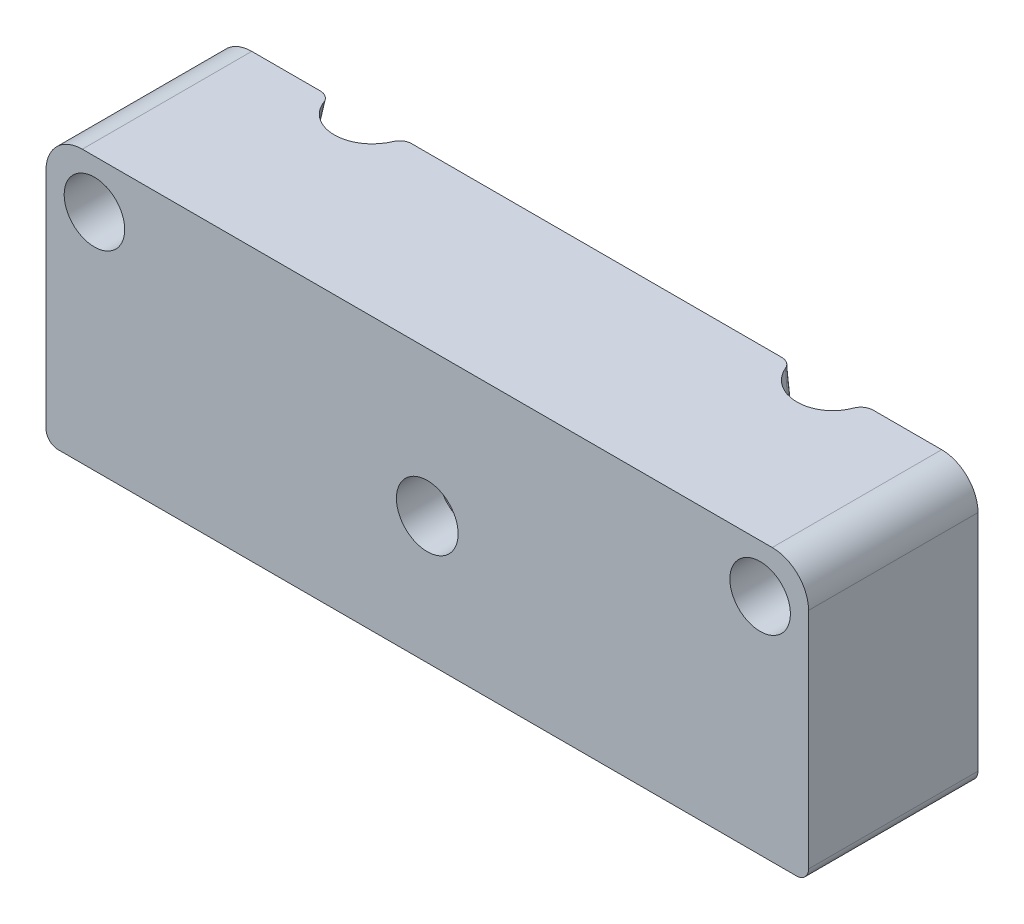
SolidWorks part; units mm, degrees
other "Extruder Parking Post Base" parameters "D3"=9.4899, "D4"=7.1672, "D1"=20.5784, "D2"=74.5967, "D5"=5, "D6"=5, "D7"=3.2, "D8"=4
ref_plane "Front" through (0, 0, 0) normal (0, 0, 1) x (1, 0, 0)
ref_plane "Top" through (0, 0, 0) normal (0, 1, 0) x (1, 0, 0)
ref_plane "Right" through (0, 0, 0) normal (1, 0, 0) x (0, 0, -1)
sketch "Sketch1" plane through (0, 0, 0) normal (0, 1, 0) x (1, 0, 0)
  line L0 (0, 10) -> (8, 10) construction
  line L1 (0, 0) -> (63, 0)
  line L2 (0, 0) -> (0, 20)
  line L3 (0, 20) -> (63, 20)
  line L4 (63, 0) -> (63, 20)
  line L5 (63, 10) -> (55, 10) construction
  circle A0 centre (55, 10) radius 2.65
  circle A1 centre (8, 10) radius 2.65
  dimension "D4" = 5.3
  dimension "D1" = 20
  dimension "D2" = 63
  dimension "D3" = 8
extrude "Boss-Extrude1" add sketch "Sketch1" along normal blind 5
sketch "Sketch2" plane through (0, 5, 0) normal (0, 1, 0) x (1, 0, 0)
  line L0 (31.5, 20) -> (31.5, 0) construction
  line L1 (63, 20) -> (0, 20) construction
  line L2 (0, 0) -> (63, 0) construction
  line L3 (27.5, 8.2) -> (35.5, 8.2)
  line L4 (35.5, 8.2) -> (35.5, 12)
  line L5 (35.5, 12) -> (46.5, 12)
  line L6 (46.5, 12) -> (46.5, 4)
  line L7 (46.5, 4) -> (16.5, 4)
  line L8 (16.5, 12) -> (16.5, 4)
  line L9 (27.5, 12) -> (16.5, 12)
  line L10 (27.5, 8.2) -> (27.5, 12)
  point P15 (31.5, 4)
  point P17 (31.5, 8.2)
  dimension "D1" = 8
  dimension "D2" = 3.8
  dimension "D3" = 30
  dimension "D4" = 4
  dimension "D5" = 8
extrude "Boss-Extrude2" add sketch "Sketch2" along normal blind 22
sketch "Sketch3" plane through (0, 0, -8.2) normal (0, 0, -1) x (-1, 0, 0)
  line L0 (-31.5, 27) -> (-31.5, 19.75) construction
  line L1 (-35.5, 27) -> (-27.5, 27) construction
  line L2 (-31.5, 19.75) -> (-31.5, 16.25) construction
  line L3 (-31.5, 16.25) -> (-31.5, 5) construction
  line L4 (-63, 5) -> (0, 5) construction
  line L5 (-31.5, 19.75) -> (-31.5, 16.25) construction
  line L6 (-29.9, 19.75) -> (-29.9, 16.25)
  line L7 (-33.1, 19.75) -> (-33.1, 16.25)
  arc A0 (-29.9, 19.75) -> (-33.1, 19.75) centre (-31.5, 19.75) ccw
  arc A1 (-33.1, 16.25) -> (-29.9, 16.25) centre (-31.5, 16.25) ccw
  point P9 (-31.5, 18)
  dimension "D2" = 1.6
  dimension "D1" = 13
  dimension "D3" = 3.5
extrude "Cut-Extrude1" cut sketch "Sketch3" against normal through all
fillet "Fillet1" radius 2 4 edges at (0, 2.5, -20) (0, 2.5, 0) (63, 2.5, -20) (63, 2.5, 0)
ref_plane "Plane1" through (0, 8, 0) normal (0, 1, 0) x (1, 0, 0)
sketch "Sketch4" plane through (0, 0, -4) normal (0, 0, 1) x (1, 0, 0)
  line L0 (31.5, 0) -> (31.5, 30) construction
  line L1 (2, 0) -> (61, 0) construction
  line L2 (0, 30) -> (63, 30)
  line L3 (63, 30) -> (63, 5)
  line L4 (63, 5) -> (0, 5)
  line L5 (16.5, 27) -> (46.5, 27) construction
  line L7 (0, 30) -> (0, 5)
  line L8 (2, 5) -> (61, 5) construction
  line L9 (31.5, 19.75) -> (31.5, 16.25) construction
  line L10 (63, 0) -> (63, 5) construction
  circle A1 centre (59, 26) radius 2.5
  circle A2 centre (4, 26) radius 2.5
  circle A3 centre (31.5, 18) radius 2.55
  point P12 (31.5, 5)
  point P21 (31.5, 18)
  dimension "D4" = 5
  dimension "D7" = 5.1
  dimension "D1" = 3
  dimension "D5" = 4
  dimension "D6" = 4
  dimension "D2" = 27.5
extrude "Boss-Extrude3" add sketch "Sketch4" along normal up to surface (4 mm away) separate body up to face at (31.5, 2.5, 0)
chamfer "Chamfer4" distance 0.5 angle 15 1 edges at (34.05, 18, -4)
sketch "Sketch6" plane through (0, 0, -4) normal (0, 0, -1) x (-1, 0, 0)
  line L0 (0, 30) -> (0, 5) construction
  line L1 (-63, 30) -> (0, 30) construction
  line L2 (-63, 5) -> (-63, 30) construction
  line L3 (0, 30) -> (0, 5)
  line L4 (-63, 30) -> (0, 30)
  line L5 (-63, 5) -> (-63, 30)
  line L6 (-63, 5) -> (-60, 5)
  line L7 (0, 5) -> (-63, 5) construction
  line L8 (-60, 5) -> (-60, 21.5)
  line L9 (-60, 21.5) -> (-54.5, 21.5)
  line L10 (-54.5, 21.5) -> (-54.5, 27)
  line L11 (-54.5, 27) -> (-8.5, 27)
  line L12 (-35.5, 27) -> (-27.5, 27) construction
  line L13 (-31.5, 27) -> (-31.5, 30) construction
  line L14 (0, 5) -> (-3, 5)
  line L15 (-3, 5) -> (-3, 21.5)
  line L16 (-3, 21.5) -> (-8.5, 21.5)
  line L17 (-8.5, 21.5) -> (-8.5, 27)
  circle A0 centre (-59, 26) radius 2.5 construction
  circle A1 centre (-4, 26) radius 2.5 construction
  circle A2 centre (-4, 26) radius 2.5
  circle A3 centre (-59, 26) radius 2.5
  dimension "D1" = 3
  dimension "D2" = 3
  dimension "D3" = 4.5
extrude "Boss-Extrude4" add sketch "Sketch6" along normal blind 10
other "Move Face1" face at (31.5, 5, -8) parameters "D1"=2.5
fillet "Fillet2" radius 3 3 edges at (3, 21.5, -9) (63, 30, -7) (54.5, 21.5, -9)
fillet "Fillet6" radius 3 3 edges at (60, 21.5, -9) (8.5, 21.5, -9) (54.5, 27, -9)
fillet "Fillet7" radius 3 2 edges at (8.5, 27, -9) (0, 30, -7)
fillet "Fillet3" radius 1 4 edges at (63, 7.5, -7) (60, 7.5, -9) (0, 7.5, -7) (3, 7.5, -9)
other "Move Face3" [suppressed] parameters "D1"=2
fillet "Fillet4" radius 0.5 1 edges at (31.5, 27, -4)
sketch3d "3DSketch1"
  line L0 (8, 5, -10) -> (13.2094, 34.0813, -15.2094) construction
  line L1 (8, 5, -10) -> (8, 0, -10) construction
  line L2 (8, 5, -10) -> (8, 5, -14.8927) construction
  line L3 (8, 5, -10) -> (13.6162, 5, -10) construction
  dimension "D1" = 80
  dimension "D2" = 30
  dimension "D3" = 80
ref_plane "Plane2" through (13.2094, 34.0813, -15.2094) normal (0.1736, 0.9694, -0.1736) x (0.9848, -0.171, 0.0304)
sketch "Sketch7" plane through (13.2094, 34.0813, -15.2094) normal (0.1736, 0.9694, -0.1736) x (0.9848, -0.171, 0.0304)
  circle A0 centre (0, 0) radius 3
  dimension "D1" = 6
extrude "Cut-Extrude2" cut sketch "Sketch7" against normal up to surface (30.5457 mm away) contours A0
fillet "Fillet5" radius 1 2 edges at (15.2429, 28.5046, -14) (8.8683, 26.8298, -14)
other "Move Face4" [suppressed] parameters "D1"=8
fillet "Fillet8" [suppressed] radius 4
ref_plane "Plane3" through (31.5, 0, 0) normal (-1, 0, 0) x (0, 0, 1)
mirror "Mirror2" about plane through (31.5, 0, 0) normal (-1, 0, 0) of "Cut-Extrude2", "Fillet5"
delete or keep bodies "Body-Delete/Keep 1" type delete bodies bodies 103
delete or keep bodies "Body-Delete/Keep 2" [suppressed] type delete bodies bodies 113
equation "\"dowel_pin_spacing\"= 55"
equation "\"D2@Sketch1\"=\"dowel_pin_spacing\" + 8"
equation "\"D2@Sketch4\"=\"dowel_pin_spacing\"/2"
